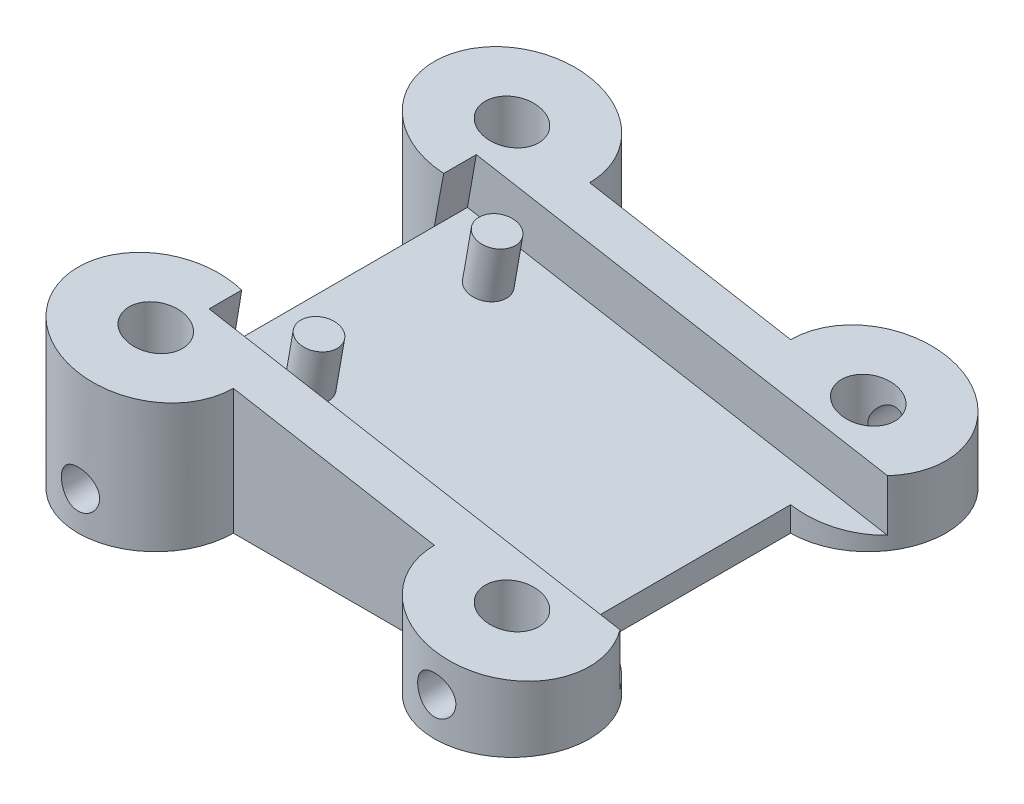
SolidWorks part; units mm, degrees
ref_plane "Front Plane" through (0, 0, 0) normal (0, 0, 1) x (1, 0, 0)
ref_plane "Top Plane" through (0, 0, 0) normal (0, 1, 0) x (1, 0, 0)
ref_plane "Right Plane" through (0, 0, 0) normal (1, 0, 0) x (0, 0, -1)
sketch "Sketch1" plane through (0, 0, 0) normal (0, 1, 0) x (1, 0, 0)
  line L0 (14, 28) -> (14, 0) construction
  line L1 (0, 0) -> (28, 0)
  line L2 (0, 0) -> (0, 28)
  line L3 (0, 28) -> (28, 28)
  line L4 (28, 0) -> (28, 28)
  line L5 (0, 14) -> (28, 14) construction
  point P9 (14, 14)
  dimension "D1" = 28
extrude "Boss-Extrude1" add sketch "Sketch1" along normal blind 10.9372
sketch "Sketch2" plane through (0, 0, 0) normal (0, 0, 1) x (1, 0, 0)
  line L0 (0, 10.9372) -> (28, 6)
  line L1 (0, 10.9372) -> (28, 10.9372) construction
  line L2 (28, 10.9372) -> (28, 0) construction
  line L3 (0, 10.9372) -> (28, 10.9372)
  line L4 (28, 10.9372) -> (28, 6)
  dimension "D2" = 6
  dimension "D3" = 10
extrude "Cut-Extrude1" cut sketch "Sketch2" against normal through all
sketch "Sketch3" plane through (1.8704, 10.6074, 0) normal (0.1736, 0.9848, 0) x (0.9848, -0.1736, 0)
  line L0 (-1.8992, 28) -> (-1.8992, 0) construction
  line L1 (-1.8992, 3.5) -> (48.1008, 3.5)
  line L2 (-1.8992, 3.5) -> (-1.8992, 24.5)
  line L3 (-1.8992, 24.5) -> (48.1008, 24.5)
  line L4 (48.1008, 3.5) -> (48.1008, 24.5)
  point P9 (-1.8992, 14)
  point P10 (-1.8992, 14)
  dimension "D1" = 21
  dimension "D2" = 50
extrude "Cut-Extrude2" cut sketch "Sketch3" against normal blind 4
ref_plane "Plane1" through (0, 10.9372, 0) normal (0, 1, 0) x (1, 0, 0)
sketch "Sketch11" plane through (1.1758, 6.6681, 0) normal (0.1736, 0.9848, 0) x (0.9848, -0.1736, 0)
  line L0 (27.238, 24.5) -> (-1.1939, 24.5) construction
  line L1 (27.238, 24.5) -> (27.238, 3.5) construction
  line L2 (-1.1939, 3.5) -> (27.238, 3.5) construction
  line L3 (27.238, 24.5) -> (-1.1939, 24.5) construction
  line L4 (27.238, 24.5) -> (27.238, 3.5) construction
  line L5 (-1.1939, 3.5) -> (27.238, 3.5) construction
  line L6 (13.0221, 3) -> (13.0221, 50003) construction
  line L7 (24.633, 14) -> (-49975.367, 14) construction
  circle A2 centre (4.0221, 21) radius 1.45
  circle A3 centre (4.0221, 7) radius 1.45
  point P6 (13.0221, 3.5)
  point P9 (27.238, 14)
  dimension "D4" = 2.9
  dimension "D5" = 9
  dimension "D6" = 7
extrude "Boss-Extrude2" add sketch "Sketch11" along normal blind 4
sketch "Sketch12" plane through (0, 10.9372, 0) normal (0, 1, 0) x (1, 0, 0)
  line L0 (0, 3.5) -> (0, 24.5) construction
  line L1 (0, 3.5) -> (28, 3.5) construction
  line L2 (0, 3.5) -> (0, 24.5) construction
  line L3 (0, 3.5) -> (28, 3.5) construction
  line L4 (0, 14) -> (50000, 14) construction
  line L5 (14, 4) -> (14, 50004) construction
  circle A0 centre (14, 14) radius 7
  point P7 (0, 14)
  point P10 (14, 3.5)
  dimension "D1" = 14
sketch "Sketch13" plane through (0, 0, 0) normal (0, -1, 0) x (1, 0, 0)
  line L0 (0, 0) -> (28, 0) construction
  line L1 (28, 0) -> (28, -28) construction
  line L2 (28, -28) -> (0, -28) construction
  line L3 (0, -28) -> (0, 0) construction
  line L4 (0, 0) -> (28, 0) construction
  line L5 (28, 0) -> (28, -28) construction
  line L6 (28, -28) -> (0, -28) construction
  line L7 (0, -28) -> (0, 0) construction
  line L8 (0, -14) -> (28, -14) construction
  line L9 (14, -28) -> (14, 0) construction
  circle A0 centre (0, 0) radius 2.1
  circle A1 centre (28, 0) radius 2.1
  circle A2 centre (28, -28) radius 2.1
  circle A3 centre (0, -28) radius 2.1
  dimension "D1" = 4.2
  dimension "D2" = 2
  dimension "D3" = 2
extrude "Cut-Extrude5" cut sketch "Sketch13" against normal through all
sketch "Sketch14" plane through (0, 0, 0) normal (0, -1, 0) x (1, 0, 0)
  line L0 (28, -3.5) -> (28, -2.1) construction
  line L1 (2.1, -28) -> (25.9, -28) construction
  line L2 (0, -3.5) -> (0, -24.5) construction
  circle A0 centre (0, 0) radius 2.1 construction
  circle A1 centre (0, 0) radius 2.1 construction
  circle A2 centre (0, 0) radius 6.1
  circle A3 centre (0, 0) radius 2.1
  circle A4 centre (28, 0) radius 2.1
  circle A5 centre (28, 0) radius 6.1
  circle A6 centre (28, -28) radius 2.1
  circle A7 centre (28, -28) radius 6.1
  circle A8 centre (0, -28) radius 2.1
  circle A9 centre (0, -28) radius 6.1
  dimension "D1" = 4
  dimension "D4" = 4.2
  dimension "D2" = 2
  dimension "D3" = 2
extrude "Boss-Extrude3" add sketch "Sketch14" against normal up to surface (10.9372 mm away) up to face at (14, 8.4686, -25.9884)
sketch "Sketch15" plane through (0, 0, -28) normal (0, 0, -1) x (-1, 0, 0)
  line L0 (-21.9, 0) -> (-6.1, 0) construction
  line L1 (-21.9, 0) -> (-0.9, 0) construction
  line L4 (-14, 8.4686) -> (-14, 0) construction
  line L5 (-6.1, 9.8616) -> (-21.9, 7.0756) construction
  circle A0 centre (-28, 3) radius 1.5
  circle A1 centre (0, 3) radius 1.5
  point P4 (-28, 0)
  dimension "D1" = 3
  dimension "D2" = 3
extrude "Cut-Extrude6" cut sketch "Sketch15" along normal through all
sketch "Sketch16" plane through (0, 0, 0) normal (0, 0, 1) x (1, 0, 0)
  circle A0 centre (0, 3) radius 1.5 construction
  circle A1 centre (28, 3) radius 1.5 construction
  circle A2 centre (0, 3) radius 1.5
  circle A3 centre (28, 3) radius 1.5
extrude "Cut-Extrude7" cut sketch "Sketch16" along normal through all
sketch "Sketch18" plane through (1.8704, 10.6074, 0) normal (0.1736, 0.9848, 0) x (0.9848, -0.1736, 0)
  line L5 (-1.8992, 3.5) -> (25.6754, 3.5) construction
  line L8 (3.1739, 3.5) -> (21.4597, 3.5) construction
  line L9 (3.1739, 3.5) -> (21.4597, 3.5) construction
  line L22 (3.8792, 24.5) -> (-1.1939, 24.5)
  line L37 (6.4597, 3.5) -> (36.4597, 3.5)
  line L38 (6.4597, 3.5) -> (6.4597, 24.5)
  line L39 (6.4597, 24.5) -> (36.4597, 24.5)
  line L40 (36.4597, 3.5) -> (36.4597, 24.5)
  line L42 (-1.1939, 24.5) -> (-1.1939, 21.9)
  line L46 (-1.1939, 6.1) -> (-1.1939, 3.5)
  line L47 (-1.1939, 3.5) -> (3.8792, 3.5)
  line L49 (3.1739, 24.5) -> (21.4597, 24.5) construction
  ellipse E1 centre (-1.1939, 28) end of major axis (5.0002, 28) minor radius 6.1 (-1.1939, 21.9) -> (3.8792, 24.5) ccw construction
  ellipse E2 centre (-1.1939, 28) end of major axis (5.0002, 28) minor radius 6.1 (-1.1939, 21.9) -> (3.8792, 24.5) ccw
  ellipse E3 centre (-1.1939, 0) end of major axis (5.0002, 0) minor radius 6.1 (3.8792, 3.5) -> (-1.1939, 6.1) ccw construction
  ellipse E4 centre (-1.1939, 0) end of major axis (5.0002, 0) minor radius 6.1 (3.8792, 3.5) -> (-1.1939, 6.1) ccw
  point P7 (21.4597, 3.5)
  dimension "D1" = 30
extrude "Cut-Extrude8" cut sketch "Sketch18" against normal up to surface (4 mm away) up to face at (6.5647, 5.7179, -21)
equation "\"TrackLength\"= 150"
equation "\"MarbleWidth\"= 13"
equation "\"MarbleTrackWidth\"= \"MarbleWidth\" - 1"
equation "\"TrackWidth\"= \"MarbleTrackWidth\" + ( 2 * 4 )"
equation "\"MarbleTrackLength\"= \"TrackLength\" - ( 2 * 8 )"
equation "\"MountWidth\"= \"TrackWidth\" + 8"
equation "\"D1@Sketch1\"=\"MountWidth\""
equation "\"D1@Boss-Extrude1\"=\"RampHeight\""
equation "\"RampDepth\"=6"
equation "\"RampAngle\" = 10"
equation "\"RampHeight\"= ( \"MountWidth\" * tan ( \"RampAngle\" ) ) + \"RampDepth\""
equation "\"D1@Sketch3\"=\"TrackWidth\" + 1"
equation "\"MountWidth\"= \"TrackWidth\" + 10"
equation "\"MountLength\"=66.6651"
